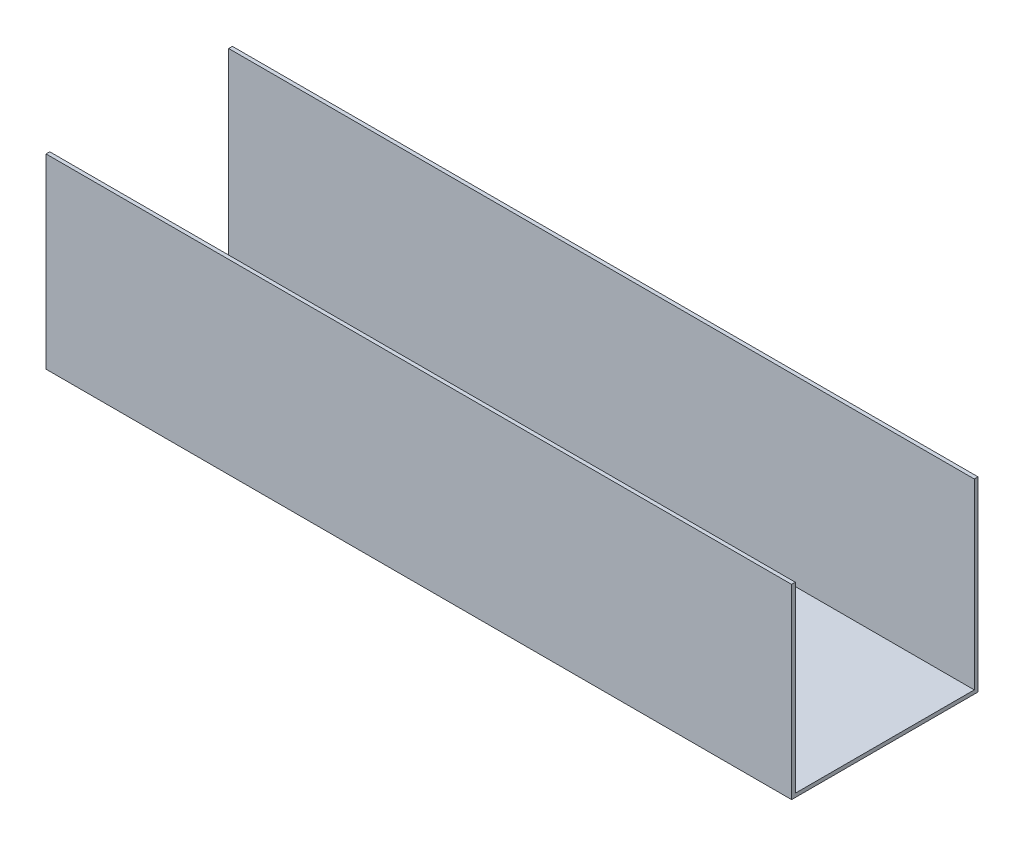
SolidWorks part; units mm, degrees
ref_plane "Ebene vorne" through (0, 0, 0) normal (0, 0, 1) x (1, 0, 0)
ref_plane "Ebene oben" through (0, 0, 0) normal (0, 1, 0) x (1, 0, 0)
ref_plane "Ebene rechts" through (0, 0, 0) normal (1, 0, 0) x (0, 0, -1)
sketch "Sketch1" plane through (0, 0, 0) normal (1, 0, 0) x (0, 0, -1)
  line L0 (0, 100.0239) -> (2, 100.0239)
  line L1 (0, 0) -> (100, 0)
  line L2 (0, 0) -> (0, 100.0239)
  line L3 (98, 100) -> (100, 100)
  line L4 (100, 0) -> (100, 100)
  line L5 (2, 2) -> (98, 2)
  line L6 (2, 2) -> (2, 100.0239)
  line L8 (98, 2) -> (98, 100)
  dimension "D1" = 2
  dimension "D3" = 2
  dimension "D4" = 2
  dimension "D5" = 100
  dimension "D6" = 100
extrude "Boss-Extrude1" add sketch "Sketch1" along normal blind 400
